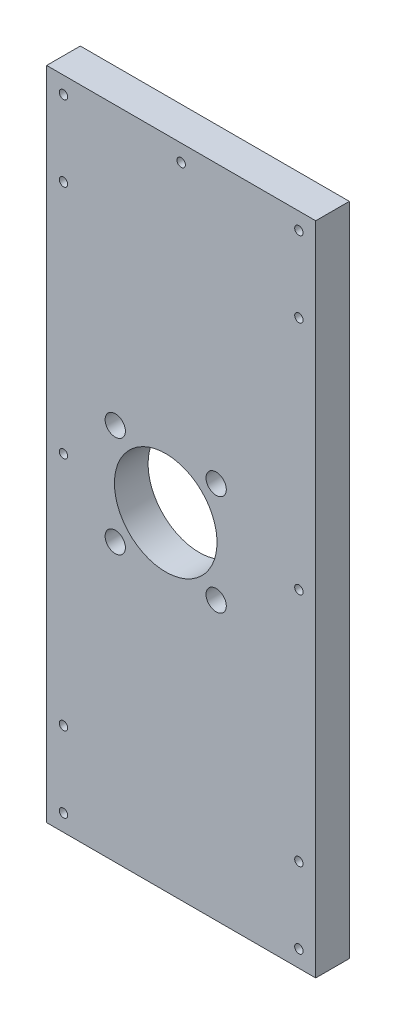
SolidWorks part; units mm, degrees
ref_plane "Ebene vorne" through (0, 0, 0) normal (0, 0, 1) x (1, 0, 0)
ref_plane "Ebene oben" through (0, 0, 0) normal (0, 1, 0) x (1, 0, 0)
ref_plane "Ebene rechts" through (0, 0, 0) normal (1, 0, 0) x (0, 0, -1)
sketch "Skizze1" plane through (0, 0, 0) normal (0, 0, 1) x (1, 0, 0)
  line L1 (-69.0594, 70.0995) -> (10.9406, 70.0995)
  line L2 (-69.0594, 70.0995) -> (-69.0594, -124.9005)
  line L3 (-69.0594, -124.9005) -> (10.9406, -124.9005)
  line L4 (10.9406, 70.0995) -> (10.9406, -124.9005)
  dimension "D1" = 195
  dimension "D2" = 80
extrude "Aufsatz-Linear austragen1" add sketch "Skizze1" against normal blind 10
sketch "Skizze2" plane through (0, 0, -10) normal (0, 0, -1) x (-1, 0, 0)
  line L0 (33.6594, 70.0995) -> (33.6594, -124.9005) construction
  line L1 (-10.9406, 70.0995) -> (69.0594, 70.0995) construction
  line L2 (69.0594, -124.9005) -> (-10.9406, -124.9005) construction
  line L3 (33.6594, -27.4005) -> (69.0594, -27.4005) construction
  line L4 (69.0594, 70.0995) -> (69.0594, -124.9005) construction
  line L5 (18.6594, -12.4005) -> (48.6594, -12.4005) construction
  line L6 (48.6594, -12.4005) -> (48.6594, -42.4005) construction
  line L7 (48.6594, -42.4005) -> (18.6594, -42.4005) construction
  line L8 (18.6594, -42.4005) -> (18.6594, -12.4005) construction
  line L9 (18.6594, -12.4005) -> (48.6594, -42.4005) construction
  circle A0 centre (18.6594, -12.4005) radius 3.015
  circle A1 centre (48.6594, -12.4005) radius 3.015
  circle A2 centre (18.6594, -42.4005) radius 3.015
  circle A3 centre (48.6594, -42.4005) radius 3.015
  circle A4 centre (33.6594, -27.4005) radius 15.25
  point P22 (33.6594, -27.4005)
  dimension "D1" = 30
  dimension "D3" = 6.03
  dimension "D2" = 30
  dimension "D4" = 35.4
extrude "Schnitt-Linear austragen1" cut sketch "Skizze2" against normal blind 10
sketch "Skizze3" plane through (0, 0, -10) normal (0, 0, -1) x (-1, 0, 0)
  line L0 (-5.9406, 65.0995) -> (64.0594, 65.0995) construction
  line L1 (29.0594, 65.0995) -> (29.0594, 70.0995) construction
  line L2 (-10.9406, 70.0995) -> (69.0594, 70.0995) construction
  line L3 (69.0594, 70.0995) -> (69.0594, -124.9005) construction
  line L4 (-5.9406, -119.9005) -> (64.0594, -119.9005) construction
  line L5 (29.0594, -119.9005) -> (29.0594, -124.9005) construction
  line L6 (69.0594, -124.9005) -> (-10.9406, -124.9005) construction
  line L7 (-5.9406, 42.5995) -> (-5.9406, -27.4005) construction
  line L8 (-5.9406, 42.5995) -> (-5.9406, 65.0995) construction
  line L9 (-5.9406, -27.4005) -> (-5.9406, -97.4005) construction
  line L10 (64.0594, 42.5995) -> (64.0594, 65.0995) construction
  line L11 (64.0594, -97.4005) -> (64.0594, -27.4005) construction
  line L12 (-5.9406, -97.4005) -> (-5.9406, -119.9005) construction
  line L13 (64.0594, -97.4005) -> (64.0594, -119.9005) construction
  line L15 (64.0594, -27.4005) -> (64.0594, 42.5995) construction
  circle A0 centre (29.0594, 65.0995) radius 2.5
  circle A1 centre (-5.9406, 65.0995) radius 2.5
  circle A2 centre (64.0594, 65.0995) radius 2.5
  circle A3 centre (29.0594, -119.9005) radius 2.5
  circle A4 centre (-5.9406, -119.9005) radius 2.5
  circle A5 centre (64.0594, -119.9005) radius 2.5
  circle A6 centre (-5.9406, 42.5995) radius 2.5
  circle A7 centre (-5.9406, -27.4005) radius 2.5
  circle A9 centre (-5.9406, -97.4005) radius 2.5
  circle A10 centre (64.0594, -97.4005) radius 2.5
  circle A12 centre (64.0594, -27.4005) radius 2.5
  circle A13 centre (64.0594, 42.5995) radius 2.5
  dimension "D3" = 5
  dimension "D1" = 5
  dimension "D2" = 5
  dimension "D4" = 70
extrude "Schnitt-Linear austragen2" cut sketch "Skizze3" against normal blind 5
sketch "Skizze6" plane through (0, 0, 0) normal (0, 0, 1) x (1, 0, 0)
  line L0 (-64.0594, 65.0995) -> (-64.0594, 42.5995) construction
  line L2 (-64.0594, 42.5995) -> (-64.0594, -27.4005) construction
  line L3 (-64.0594, -27.4005) -> (-64.0594, -97.4005) construction
  line L4 (-64.0594, -97.4005) -> (-64.0594, -119.9005) construction
  line L5 (-64.0594, 65.0995) -> (5.9406, 65.0995) construction
  line L6 (5.9406, -119.9005) -> (5.9406, -97.4005) construction
  line L7 (5.9406, -97.4005) -> (5.9406, -27.4005) construction
  line L8 (5.9406, -27.4005) -> (5.9406, 42.5995) construction
  line L10 (5.9406, 42.5995) -> (5.9406, 65.0995) construction
  line L11 (-64.0594, -119.9005) -> (5.9406, -119.9005) construction
  line L12 (10.9406, 70.0995) -> (-69.0594, 70.0995) construction
  line L14 (-29.0594, 65.0995) -> (-29.0594, 70.0995) construction
  line L15 (-69.0594, -124.9005) -> (10.9406, -124.9005) construction
  circle A0 centre (-64.0594, 65.0995) radius 1.25
  circle A1 centre (-29.0594, 65.0995) radius 1.25
  circle A2 centre (5.9406, 65.0995) radius 1.25
  circle A3 centre (-64.0594, 42.5995) radius 1.25
  circle A5 centre (-64.0594, -27.4005) radius 1.25
  circle A6 centre (-64.0594, -97.4005) radius 1.25
  circle A7 centre (-64.0594, -119.9005) radius 1.25
  circle A8 centre (5.9406, -119.9005) radius 1.25
  circle A9 centre (5.9406, -97.4005) radius 1.25
  circle A10 centre (5.9406, -27.4005) radius 1.25
  circle A12 centre (5.9406, 42.5995) radius 1.25
  point P16 (-64.0594, 17.8779)
  dimension "D2" = 2.5
  dimension "D1" = 5
  dimension "D3" = 5
  dimension "D4" = 70
extrude "Schnitt-Linear austragen4" cut sketch "Skizze6" against normal blind 5
